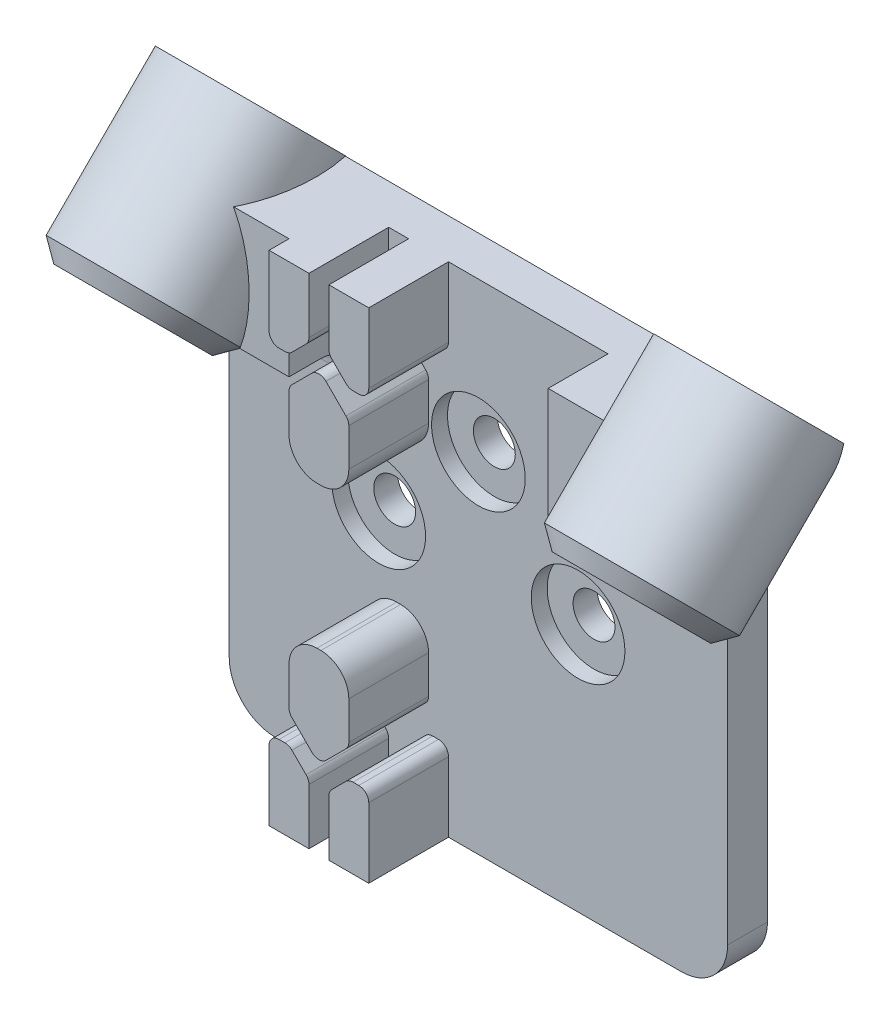
SolidWorks part; units mm, degrees
ref_plane "Piano frontale" through (0, 0, 0) normal (0, 0, 1) x (1, 0, 0)
ref_plane "Piano superiore" through (0, 0, 0) normal (0, 1, 0) x (1, 0, 0)
ref_plane "Piano destro" through (0, 0, 0) normal (1, 0, 0) x (0, 0, -1)
sketch "Schizzo1" plane through (0, 0, 0) normal (0, 0, 1) x (1, 0, 0)
  line L0 (25, 3.35) -> (19.75, 3.35) construction
  line L1 (25, 3.35) -> (25, 20.365)
  line L2 (20.365, 25) -> (-20.365, 25)
  line L3 (-25, 20.365) -> (-25, 3.35)
  line L4 (-19.75, 3.35) -> (-25, 3.35) construction
  line L5 (-19.75, -3.35) -> (-19.75, 3.35) construction
  line L6 (-25, -3.35) -> (-19.75, -3.35) construction
  line L7 (-25, -3.35) -> (-25, -20.365)
  line L8 (-20.365, -25) -> (20.365, -25)
  line L9 (25, -20.365) -> (25, -3.35)
  line L10 (19.75, -3.35) -> (25, -3.35) construction
  line L11 (19.75, 3.35) -> (19.75, -3.35) construction
  line L12 (0, 25) -> (0, -25) construction
  line L13 (25, 3.35) -> (25, -3.35)
  line L14 (-25, 3.35) -> (-25, -3.35)
  arc A0 (25, 20.365) -> (20.365, 25) centre (20.365, 20.365) ccw
  arc A1 (-20.365, 25) -> (-25, 20.365) centre (-20.365, 20.365) ccw
  arc A2 (-25, -20.365) -> (-20.365, -25) centre (-20.365, -20.365) ccw
  arc A3 (20.365, -25) -> (25, -20.365) centre (20.365, -20.365) ccw
  circle A4 centre (-15, -15.95) radius 5.05 construction
  circle A5 centre (15, -15.95) radius 5.05 construction
  circle A6 centre (15, 15.95) radius 6 construction
  circle A7 centre (-15, 15.95) radius 6 construction
  circle A8 centre (0, 10) radius 2.1
  circle A9 centre (-10, 0) radius 2.1
  circle A10 centre (0, 0) radius 2.1 construction
  circle A11 centre (0, -10) radius 2.1 construction
  circle A12 centre (10, 0) radius 2.1
  point P0 (25, 11.8575)
  dimension "D2" = 4.2
  dimension "D7" = 12
  dimension "D12" = 4.635
  dimension "D14" = 10.1
  dimension "D15" = 19.75
  dimension "D16" = 3.35
  dimension "D1" = 50
  dimension "D3" = 10
  dimension "D4" = 10
  dimension "D5" = 10
  dimension "D6" = 10
  dimension "D8" = 30
  dimension "D9" = 31.9
  dimension "D10" = 9.05
  dimension "D11" = 10
  dimension "D13" = 50
extrude "Estrusione-Estrusione1" add sketch "Schizzo1" along normal blind 4
sketch "Schizzo4" plane through (0, 0, 4) normal (0, 0, 1) x (1, 0, 0)
  line L0 (0, 25) -> (0, -25) construction
  line L1 (20.365, 25) -> (-20.365, 25) construction
  line L2 (-20.365, -25) -> (20.365, -25) construction
  line L3 (-8, 25) -> (-8, -25) construction
  line L4 (-7, -25) -> (-7, -19)
  line L5 (-13, -25) -> (-9, -25)
  line L6 (-13, -25) -> (-13, -17)
  line L7 (-13, -17) -> (-11, -17)
  line L8 (-9, -25) -> (-9, -19)
  line L9 (-3, -17) -> (-5, -17)
  line L10 (-3, -25) -> (-3, -17)
  line L11 (-3, -25) -> (-7, -25)
  line L12 (-11, -17) -> (-9, -19)
  line L13 (-5, -17) -> (-7, -19)
  line L14 (-8, -17.1716) -> (-11, -14.1716)
  line L15 (-11, -14.1716) -> (-11, -7.1716)
  line L16 (-11, -7.1716) -> (-5, -7.1716)
  line L17 (-5, -7.1716) -> (-5, -14.1716)
  line L18 (-5, -14.1716) -> (-8, -17.1716)
  point P21 (0, 0)
  dimension "D1" = 8
  dimension "D2" = 8
  dimension "D3" = 4
  dimension "D4" = 1
  dimension "D5" = 2
  dimension "D6" = 135
  dimension "D7" = 2
  dimension "D8" = 3
  dimension "D9" = 7
extrude "Estrusione-Estrusione4" add sketch "Schizzo4" along normal blind 8
fillet "Raccordo1" radius 1 9 edges at (-3, -17, 8) (-5, -17, 8) (-13, -17, 8) (-11, -17, 8) (-5, -14.1716, 8) (-11, -14.1716, 8) (-8, -17.1716, 8) (-7, -19, 8) (-9, -19, 8)
fillet "Raccordo2" radius 2.8 2 edges at (-5, -7.1716, 8) (-11, -7.1716, 8)
ref_axis "Assi1" through (0, 0, 0) along (0, 0, 1)
mirror "Specchia1" about plane through (0, 0, 0) normal (0, 1, 0) of "Raccordo2", "Raccordo1", "Estrusione-Estrusione4"
sketch "Schizzo5" plane through (0, 0, 4) normal (0, 0, 1) x (1, 0, 0)
  circle A0 centre (-10, 0) radius 4.7
  circle A1 centre (10, 0) radius 4.7
  circle A2 centre (10, 0) radius 2.1 construction
  circle A3 centre (0, 10) radius 4.7
  dimension "D1" = 9.4
extrude "Taglio-Estrusione1" cut sketch "Schizzo5" against normal blind 1.6
sketch "Schizzo6" plane through (0, 0, 4) normal (0, 0, 1) x (1, 0, 0)
  line L0 (-25, 5) -> (25, 5) construction
  line L1 (-25, 20.365) -> (-25, -20.365) construction
  line L2 (25, -20.365) -> (25, 20.365) construction
  line L3 (-13, 25) -> (-20.365, 25) construction
  dimension "D1" = 20
ref_plane "Piano2" through (0, 0.5, -0.5) normal (0, -0.7071, 0.7071) x (1, 0, 0)
sketch "Schizzo9" plane through (0, 0, 4) normal (0, 0, 1) x (1, 0, 0)
  line L0 (13, 25) -> (20.365, 25)
  line L1 (20.365, 25) -> (-3, 25) construction
  line L2 (25, 20.365) -> (25, 13)
  line L3 (25, -20.365) -> (25, 20.365) construction
  line L4 (25, 13) -> (13, 13)
  line L5 (13, 13) -> (13, 25)
  line L6 (0, 0) -> (0, 25) construction
  line L7 (-13, 13) -> (-13, 25)
  line L8 (-25, 13) -> (-13, 13)
  line L9 (-25, 20.365) -> (-25, 13)
  line L10 (-13, 25) -> (-20.365, 25)
  arc A0 (25, 20.365) -> (20.365, 25) centre (20.365, 20.365) ccw construction
  arc A1 (25, 20.365) -> (20.365, 25) centre (20.365, 20.365) ccw
  arc A2 (-25, 20.365) -> (-20.365, 25) centre (-20.365, 20.365) cw
  dimension "D1" = 12
extrude "Estrusione-Estrusione6" add sketch "Schizzo9" along normal blind 6
sketch "Schizzo8" plane through (0, 0.5, -0.5) normal (0, -0.7071, 0.7071) x (1, 0, 0)
  line L0 (0, 0) -> (0, 50.8367) construction
  line L1 (0, 0) -> (0, 16.5) construction
  circle A0 centre (-25, 20) radius 8
  circle A1 centre (25, 20) radius 8
  dimension "D1" = 16
  dimension "D2" = 25
  dimension "D3" = 20
extrude "Estrusione-Estrusione5" add sketch "Schizzo8" against normal blind 17
sketch "Schizzo11" plane through (0, -25, 0) normal (0, -1, 0) x (1, 0, 0)
  line L1 (-51.4628, 0) -> (53.963, 0)
  line L2 (-51.4628, 0) -> (-51.4628, -17.7396)
  line L3 (-51.4628, -17.7396) -> (53.963, -17.7396)
  line L4 (53.963, 0) -> (53.963, -17.7396)
extrude "Taglio-Estrusione3" cut sketch "Schizzo11" against normal blind 65
fillet "Raccordo3" radius 2.8 2 edges at (18.7116, 13, 4) (-18.7116, 13, 4)
chamfer "Smusso3" distance 1.5 angle 45 2 edges at (25, 20.299, 19.299) (-25, 8.9853, 7.9853)
sketch "Schizzo13" plane through (0, 0.5, -0.5) normal (0, -0.7071, 0.7071) x (1, 0, 0)
  line L0 (-25, 13.5) -> (-25, 26.5) construction
  circle A0 centre (-25, 20) radius 6.5 construction
ref_plane "Piano3" through (-25, 0, 0) normal (1, 0, 0) x (0, 0.7071, 0.7071)
sketch "Schizzo14" plane through (-25, 0, 0) normal (1, 0, 0) x (0, 0.7071, 0.7071)
  line L0 (13.5, -0.7071) -> (26.5, -0.7071) construction
  line L1 (20, -0.7071) -> (20, 11.6414) construction
  line L2 (20, -3.2071) -> (20, 7.7929) construction
  line L3 (20, -3.2071) -> (20, 7.7929)
  arc A0 (20, 7.7929) -> (20, -3.2071) centre (20, 2.2929) ccw
  dimension "D1" = 11
  dimension "D2" = 3
revolve "Taglia-Rivoluzione1" cut sketch "Schizzo14" angle 360 about L3
mirror "Specchia2" about plane through (0, 0, 0) normal (1, 0, 0) of "Taglia-Rivoluzione1"
sketch "Schizzo15" plane through (0, 0.5, -0.5) normal (0, -0.7071, 0.7071) x (1, 0, 0)
  line L0 (-25, 13.5) -> (-25, 26.5) construction
  circle A0 centre (-25, 20) radius 1.7
  circle A1 centre (25, 20) radius 1.7
  dimension "D1" = 3.4
extrude "Taglio-Estrusione4" cut sketch "Schizzo15" against normal blind 65
sketch "Schizzo16" plane through (0, 12.5208, -12.5208) normal (0, 0.7071, -0.7071) x (1, 0, 0)
  line L0 (-25, -13.5) -> (-25, -26.5) construction
  circle A0 centre (-25, -20) radius 3.7
  circle A1 centre (25, -20) radius 3.7
  dimension "D1" = 7.4
extrude "Taglio-Estrusione5" cut sketch "Schizzo16" against normal blind 5
